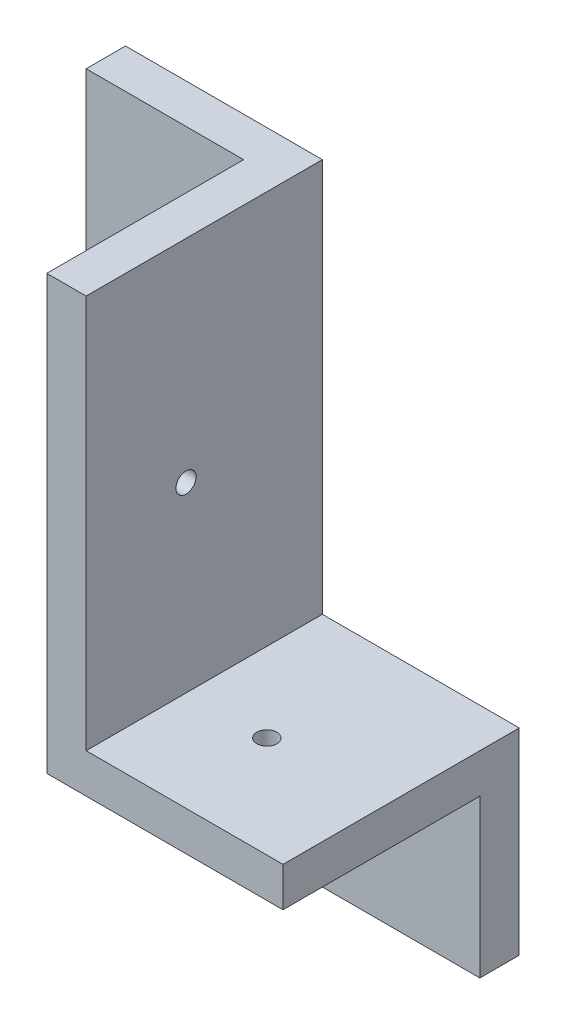
SolidWorks part; units mm, degrees
ref_plane "Front Plane" through (0, 0, 0) normal (0, 0, 1) x (1, 0, 0)
ref_plane "Top Plane" through (0, 0, 0) normal (0, 1, 0) x (1, 0, 0)
ref_plane "Right Plane" through (0, 0, 0) normal (1, 0, 0) x (0, 0, -1)
sketch "Sketch1" plane through (0, 0, 0) normal (0, 0, 1) x (1, 0, 0)
  line L0 (0, 150) -> (50, 150)
  line L1 (0, 0) -> (100, 0)
  line L2 (0, 0) -> (0, 150)
  line L3 (100, 50) -> (100, 0)
  line L5 (50, 150) -> (50, 50)
  line L6 (50, 50) -> (100, 50)
  dimension "D1" = 150
extrude "Boss-Extrude1" add sketch "Sketch1" along normal blind 10
sketch "Sketch2" plane through (0, 0, 10) normal (0, 0, 1) x (1, 0, 0)
  line L0 (40, 150) -> (40, 40)
  line L1 (50, 150) -> (0, 150) construction
  line L2 (40, 40) -> (100, 40)
  line L3 (100, 0) -> (100, 50) construction
  line L4 (100, 40) -> (100, 50)
  line L5 (100, 50) -> (50, 50)
  line L6 (50, 50) -> (50, 150)
  line L7 (50, 150) -> (40, 150)
  dimension "D1" = 10
  dimension "D2" = 10
extrude "Boss-Extrude2" add sketch "Sketch2" along normal blind 50
hole_wizard "CBORE for #10 Binding Head Machine Screw1" positions "Sketch4" profile "Sketch3" counterbore size "#10" standard "ANSI Inch" end condition through all
sketch "Sketch4" plane through (0, 0, 10) normal (0, 0, 1) x (1, 0, 0)
  point P0 (25.4168, 24.243)
sketch "Sketch3" plane through (25.4168, 24.243, 10) normal (1, 0, 0) x (0, -1, 0)
  line L0 (0, 0) -> (0, 10)
  line L1 (0, 10) -> (2.5527, 10)
  line L3 (2.5527, 10) -> (2.5527, 3.1242)
  line L4 (5.5562, 3.1242) -> (2.5527, 3.1242)
  line L5 (5.5562, 3.1242) -> (5.5563, 0.635)
  line L6 (5.5563, 0.635) -> (6.1912, 0)
  line L7 (6.1912, 0) -> (0, 0)
  line L8 (-5.5563, 0.635) -> (-6.1912, 0) construction
  line L11 (0, -6.35) -> (0, 107.95) construction
  dimension "Thru Hole Dia." = 5.1054
  dimension "Thru Hole Depth" = 10
  dimension "C'Bore Dia." = 11.1125
  dimension "C'Bore Depth" = 3.1242
  dimension "Near C'Sink Dia." = 12.3825
  dimension "Near C'Sink Angle" = 90
hole_wizard "CBORE for #10 Binding Head Machine Screw2" positions "Sketch6" profile "Sketch5" counterbore size "#10" standard "ANSI Inch" end condition through all
sketch "Sketch6" plane through (0, 0, 10) normal (0, 0, 1) x (1, 0, 0)
  point P0 (21.0222, 97.7476)
sketch "Sketch5" plane through (21.0222, 97.7476, 10) normal (1, 0, 0) x (0, -1, 0)
  line L0 (0, 0) -> (0, 10)
  line L1 (0, 10) -> (2.5527, 10)
  line L3 (2.5527, 10) -> (2.5527, 3.1242)
  line L4 (5.5562, 3.1242) -> (2.5527, 3.1242)
  line L5 (5.5562, 3.1242) -> (5.5563, 0.635)
  line L6 (5.5563, 0.635) -> (6.1912, 0)
  line L7 (6.1912, 0) -> (0, 0)
  line L8 (-5.5563, 0.635) -> (-6.1912, 0) construction
  line L11 (0, -6.35) -> (0, 107.95) construction
  dimension "Thru Hole Dia." = 5.1054
  dimension "Thru Hole Depth" = 10
  dimension "C'Bore Dia." = 11.1125
  dimension "C'Bore Depth" = 3.1242
  dimension "Near C'Sink Dia." = 12.3825
  dimension "Near C'Sink Angle" = 90
hole_wizard "CBORE for #10 Binding Head Machine Screw3" positions "Sketch8" profile "Sketch7" counterbore size "#10" standard "ANSI Inch" end condition through all
sketch "Sketch8" plane through (40, 0, 0) normal (-1, 0, 0) x (0, 0, 1)
  point P0 (34.6365, 96.2987)
sketch "Sketch7" plane through (40, 96.2987, 34.6365) normal (0, 1, 0) x (0, 0, 1)
  line L0 (0, 0) -> (0, 60.0001)
  line L1 (0, 60.0001) -> (2.5527, 60.0001)
  line L3 (2.5527, 60.0001) -> (2.5527, 3.1242)
  line L4 (5.5562, 3.1242) -> (2.5527, 3.1242)
  line L5 (5.5562, 3.1242) -> (5.5562, 0.635)
  line L6 (5.5562, 0.635) -> (6.1912, 0)
  line L7 (6.1912, 0) -> (0, 0)
  line L8 (-5.5562, 0.635) -> (-6.1912, 0) construction
  line L11 (0, -6.35) -> (0, 107.95) construction
  dimension "Thru Hole Dia." = 5.1054
  dimension "Thru Hole Depth" = 60.0001
  dimension "C'Bore Dia." = 11.1125
  dimension "C'Bore Depth" = 3.1242
  dimension "Near C'Sink Dia." = 12.3825
  dimension "Near C'Sink Angle" = 90
hole_wizard "CBORE for #10 Binding Head Machine Screw4" positions "Sketch10" profile "Sketch9" counterbore size "#10" standard "ANSI Inch" end condition through all
sketch "Sketch10" plane through (0, 40, 0) normal (0, -1, 0) x (-1, 0, 0)
  point P0 (-70.1528, -34.2545)
sketch "Sketch9" plane through (70.1528, 40, 34.2545) normal (1, 0, 0) x (0, 0, -1)
  line L0 (0, 0) -> (0, 110)
  line L1 (0, 110) -> (2.5527, 110)
  line L3 (2.5527, 110) -> (2.5527, 3.1242)
  line L4 (5.5562, 3.1242) -> (2.5527, 3.1242)
  line L5 (5.5562, 3.1242) -> (5.5562, 0.635)
  line L6 (5.5562, 0.635) -> (6.1912, 0)
  line L7 (6.1912, 0) -> (0, 0)
  line L8 (-5.5562, 0.635) -> (-6.1912, 0) construction
  line L11 (0, -6.35) -> (0, 107.95) construction
  dimension "Thru Hole Dia." = 5.1054
  dimension "Thru Hole Depth" = 110
  dimension "C'Bore Dia." = 11.1125
  dimension "C'Bore Depth" = 3.1242
  dimension "Near C'Sink Dia." = 12.3825
  dimension "Near C'Sink Angle" = 90
